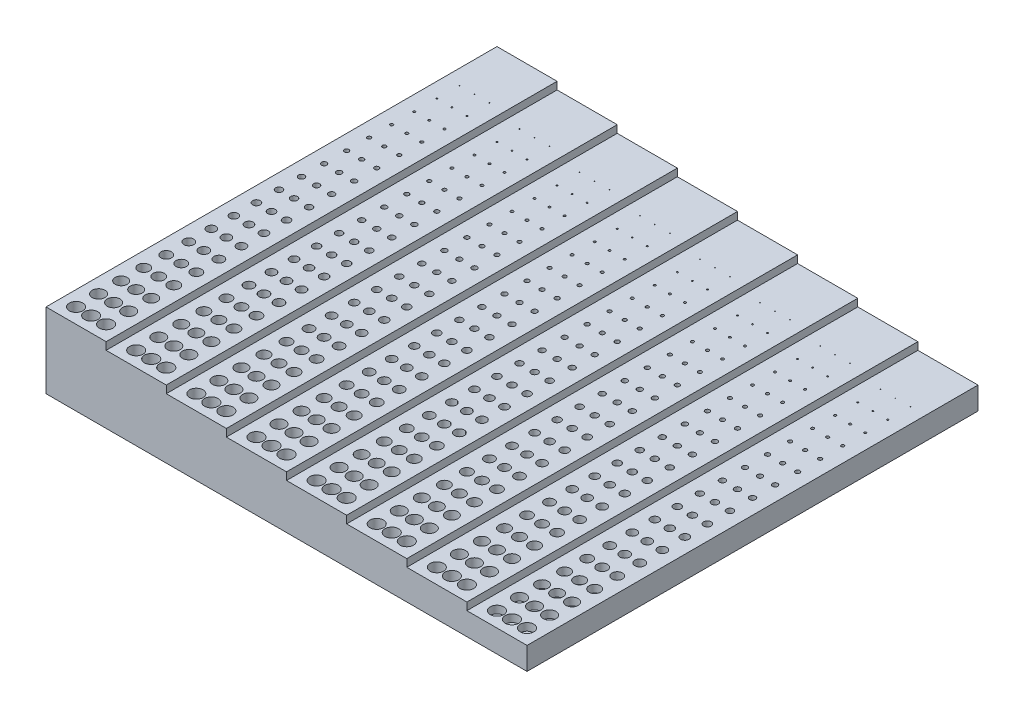
SolidWorks part; units mm, degrees
ref_plane "Front Plane" through (0, 0, 0) normal (0, 0, 1) x (1, 0, 0)
ref_plane "Top Plane" through (0, 0, 0) normal (0, 1, 0) x (1, 0, 0)
ref_plane "Right Plane" through (0, 0, 0) normal (1, 0, 0) x (0, 0, -1)
sketch "Sketch3" plane through (0, 0, 0) normal (0, 0, 1) x (1, 0, 0)
  line L0 (0, 0) -> (0, 4)
  line L1 (0, -55) -> (0, 55) construction
  line L2 (0, 4) -> (4, 4)
  line L3 (4, 4) -> (4, 3.5)
  line L4 (4, 3.5) -> (8, 3.5)
  line L5 (8, 3.5) -> (8, 3)
  line L6 (8, 3) -> (12, 3)
  line L7 (12, 3) -> (12, 2.5)
  line L8 (12, 2.5) -> (16, 2.5)
  line L9 (16, 2.5) -> (16, 2)
  line L10 (16, 2) -> (20, 2)
  line L12 (55, 0) -> (-55, 0) construction
  line L13 (32, 0) -> (0, 0)
  line L14 (20, 2) -> (20, 1.5)
  line L15 (20, 1.5) -> (24, 1.5)
  line L16 (24, 1.5) -> (24, 1)
  line L17 (24, 1) -> (28, 1)
  line L18 (28, 1) -> (28, 0.5)
  line L19 (28, 0.5) -> (32, 0.5)
  line L20 (32, 0.5) -> (32, 0)
  dimension "D1" = 4
  dimension "D2" = 4
  dimension "D3" = 0.5
extrude "Boss-Extrude1" add sketch "Sketch3" along normal blind 30
sketch "Sketch4" plane through (0, 4, 0) normal (0, 1, 0) x (1, 0, 0)
  line L0 (0, -29) -> (32, -29) construction
  line L1 (0, -2.2) -> (0, 2.2) construction
  line L2 (32, -30) -> (32, 0) construction
  line L3 (4, -30) -> (0, -30) construction
  line L4 (1, -29) -> (1, 0) construction
  line L5 (-2.2, 0) -> (2.2, 0) construction
  circle A0 centre (1, -29) radius 0.45
  circle A14 centre (1, -27.5) radius 0.425
  circle A15 centre (1, -26) radius 0.4
  circle A16 centre (1, -24.5) radius 0.375
  circle A17 centre (1, -23) radius 0.35
  circle A18 centre (1, -21.5) radius 0.325
  circle A19 centre (1, -20) radius 0.3
  circle A20 centre (1, -18.5) radius 0.275
  circle A21 centre (1, -17) radius 0.25
  circle A22 centre (1, -15.5) radius 0.225
  circle A23 centre (1, -14) radius 0.2
  circle A24 centre (1, -12.5) radius 0.175
  circle A25 centre (1, -11) radius 0.15
  circle A26 centre (1, -9.5) radius 0.125
  circle A27 centre (1, -8) radius 0.1
  circle A28 centre (1, -6.5) radius 0.075
  circle A29 centre (1, -5) radius 0.05
  circle A30 centre (1, -3.5) radius 0.025
  dimension "D3" = 0.9
  dimension "D5" = 0.8
  dimension "D4" = 0.85
  dimension "D6" = 0.75
  dimension "D7" = 0.7
  dimension "D8" = 0.65
  dimension "D9" = 0.6
  dimension "D10" = 0.55
  dimension "D11" = 0.5
  dimension "D12" = 0.45
  dimension "D13" = 0.4
  dimension "D14" = 0.35
  dimension "D15" = 0.3
  dimension "D16" = 0.25
  dimension "D17" = 0.2
  dimension "D18" = 0.15
  dimension "D19" = 0.1
  dimension "D20" = 0.05
  dimension "D1" = 1
  dimension "D2" = 1
extrude "Cut-Extrude1" cut sketch "Sketch4" against normal up to next
pattern_linear "LPattern1" count 31 spacing 1 along (1, 0, 0) skipping (3, 0), (7, 0), (11, 0), (15, 0), (19, 0), (23, 0), (27, 0) of "Cut-Extrude1"
sketch "Sketch5" plane through (0, 0, 0) normal (0, -1, 0) x (1, 0, 0)
  line L4 (0, 0) -> (32, 0)
  line L5 (32, 0) -> (32, 30)
  line L6 (32, 30) -> (0, 30)
  line L7 (0, 30) -> (0, 0)
  line L8 (0, 0) -> (32, 0)
  line L9 (32, 0) -> (32, 30)
  line L10 (32, 30) -> (0, 30)
  line L11 (0, 30) -> (0, 0)
  dimension "D1" = 0
extrude "Boss-Extrude2" add sketch "Sketch5" along normal blind 1
